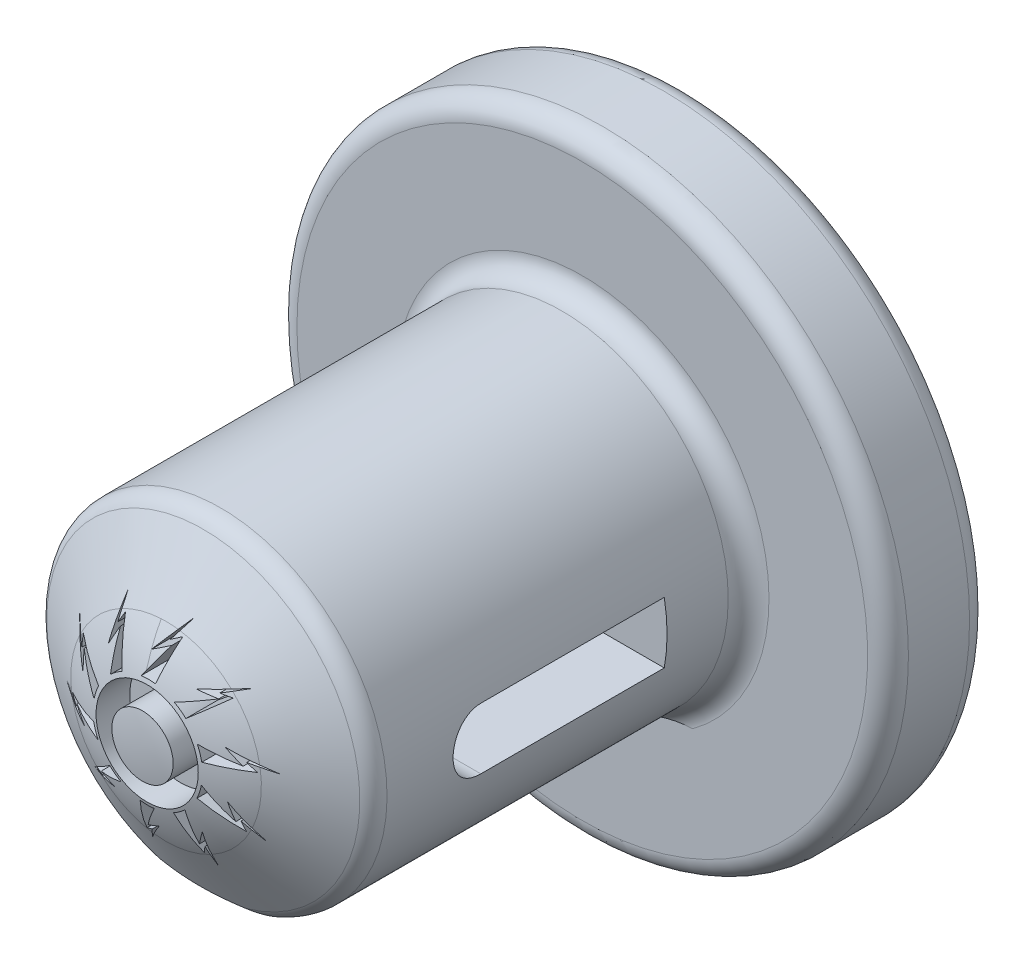
SolidWorks part; units mm, degrees
ref_plane "Alzado" through (0, 0, 0) normal (0, 0, 1) x (1, 0, 0)
ref_plane "Planta" through (0, 0, 0) normal (0, 1, 0) x (1, 0, 0)
ref_plane "Vista lateral" through (0, 0, 0) normal (1, 0, 0) x (0, 0, -1)
sketch "Croquis1" plane through (0, 0, 0) normal (0, 0, 1) x (1, 0, 0)
  line L0 (3.458, -7.3911) -> (-3.458, -7.3911)
  line L1 (2.71, -4.3911) -> (-2.71, -4.3911)
  arc A0 (2.71, -4.3911) -> (-2.71, -4.3911) centre (0, 0) ccw
  arc A1 (3.458, -7.3911) -> (-3.458, -7.3911) centre (0, 0) ccw
  point P7 (0, -4.3911)
  dimension "D1" = 10.32
  dimension "D2" = 5.42
  dimension "D3" = 3
extrude "Saliente-Extruir1" add sketch "Croquis1" along normal blind 23.3
sketch "Croquis2" plane through (0, 0, 0) normal (0, 0, -1) x (-1, 0, 0)
  line L0 (2.71, -4.3911) -> (-2.71, -4.3911) construction
  line L1 (2.71, -4.3911) -> (-2.71, -4.3911)
  circle A0 centre (0, 0) radius 15
  arc A1 (2.71, -4.3911) -> (-2.71, -4.3911) centre (0, 0) ccw construction
  arc A2 (2.71, -4.3911) -> (-2.71, -4.3911) centre (0, 0) ccw
  dimension "D1" = 30
extrude "Saliente-Extruir2" add sketch "Croquis2" against normal blind 5
sketch "Croquis3" plane through (0, 0, 0) normal (1, 0, 0) x (0, 0, -1)
  line L0 (-23.3, 0) -> (-23.3, 8.16)
  line L2 (-23.3, 8.16) -> (-25.4185, 4.6757)
  line L3 (-26.7284, 0) -> (-23.3, 0)
  arc A0 (-25.4185, 4.6757) -> (-26.7284, 0) centre (-17.7284, 0) ccw
  dimension "D2" = 9
  dimension "D1" = 31.3
revolve "Revolución1" add sketch "Croquis3" angle 360 about L3
sketch "Croquis4" plane through (0, 0, 23.3) normal (0, 0, -1) x (-1, 0, 0)
  line L1 (3.458, -7.3911) -> (-3.458, -7.3911)
  line L2 (3.458, -7.3911) -> (-3.458, -7.3911)
  arc A1 (-3.458, -7.3911) -> (3.458, -7.3911) centre (0, 0) ccw
  arc A2 (-3.458, -7.3911) -> (3.458, -7.3911) centre (0, 0) ccw
  dimension "D1" = 0
extrude "Cortar-Extruir1" cut sketch "Croquis4" against normal up to next
fillet "Redondeo3" radius 1 4 edges at (-15, 0, 0) (-15, 0, 5) (0, 8.16, 5) (0, 8.16, 23.3)
fillet "Redondeo2" radius 1 2 edges at (0, -4.3911, 0) (0, 5.16, 0)
ref_plane "Plano1" through (0, 0, 26.7284) normal (0, 0, 1) x (1, 0, 0)
sketch "Croquis5" plane through (0, 0, 26.7284) normal (0, 0, 1) x (1, 0, 0)
  line L0 (1.3026, 2.3441) -> (2.8816, 2.9738)
  line L1 (-0.324, 2.662) -> (0.5833, 4.0996)
  line L2 (0.5833, 4.0996) -> (-0.19, 3.662)
  line L3 (-0.19, 3.662) -> (1.0396, 5.192)
  line L4 (1.0396, 5.192) -> (0.4463, 4.2519)
  line L5 (0.4463, 4.2519) -> (0.876, 4.4951)
  line L6 (0.876, 4.4951) -> (0.376, 2.662)
  line L7 (2.8816, 2.9738) -> (1.9987, 3.0743)
  line L8 (1.9987, 3.0743) -> (3.8929, 3.5894)
  line L9 (3.8929, 3.5894) -> (2.8603, 3.1775)
  line L10 (2.8603, 3.1775) -> (3.3508, 3.1217)
  line L11 (3.3508, 3.1217) -> (1.8689, 1.9326)
  line L12 (2.4316, 1.1308) -> (4.0792, 0.7121)
  line L13 (4.0792, 0.7121) -> (3.4241, 1.3124)
  line L14 (3.4241, 1.3124) -> (5.2592, 0.6157)
  line L15 (5.2592, 0.6157) -> (4.1817, 0.8895)
  line L16 (4.1817, 0.8895) -> (4.5457, 0.5559)
  line L17 (4.5457, 0.5559) -> (2.6479, 0.465)
  line L18 (2.6319, -0.5144) -> (3.7187, -1.8216)
  line L19 (3.7187, -1.8216) -> (3.5415, -0.9509)
  line L20 (3.5415, -0.9509) -> (4.6166, -2.5932)
  line L21 (4.6166, -2.5932) -> (3.9059, -1.7384)
  line L22 (3.9059, -1.7384) -> (4.0044, -2.2222)
  line L23 (4.0044, -2.2222) -> (2.4155, -1.1802)
  line L24 (1.8268, -1.9632) -> (1.9378, -3.6595)
  line L25 (1.9378, -3.6595) -> (2.3062, -2.8509)
  line L26 (2.3062, -2.8509) -> (2.2107, -4.8115)
  line L27 (2.2107, -4.8115) -> (2.1381, -3.7022)
  line L28 (2.1381, -3.7022) -> (1.9334, -4.1515)
  line L29 (1.9334, -4.1515) -> (1.2605, -2.3746)
  line L30 (0.324, -2.662) -> (-0.5833, -4.0996)
  line L31 (-0.5833, -4.0996) -> (0.19, -3.662)
  line L32 (0.19, -3.662) -> (-1.0396, -5.192)
  line L33 (-1.0396, -5.192) -> (-0.4463, -4.2519)
  line L34 (-0.4463, -4.2519) -> (-0.876, -4.4951)
  line L35 (-0.876, -4.4951) -> (-0.376, -2.662)
  line L36 (-1.3026, -2.3441) -> (-2.8816, -2.9738)
  line L37 (-2.8816, -2.9738) -> (-1.9987, -3.0743)
  line L38 (-1.9987, -3.0743) -> (-3.8929, -3.5894)
  line L39 (-3.8929, -3.5894) -> (-2.8603, -3.1775)
  line L40 (-2.8603, -3.1775) -> (-3.3508, -3.1217)
  line L41 (-3.3508, -3.1217) -> (-1.8689, -1.9326)
  line L42 (-2.4316, -1.1308) -> (-4.0792, -0.7121)
  line L43 (-4.0792, -0.7121) -> (-3.4241, -1.3124)
  line L44 (-3.4241, -1.3124) -> (-5.2592, -0.6157)
  line L45 (-5.2592, -0.6157) -> (-4.1817, -0.8895)
  line L46 (-4.1817, -0.8895) -> (-4.5457, -0.5559)
  line L47 (-4.5457, -0.5559) -> (-2.6479, -0.465)
  line L48 (-2.6319, 0.5144) -> (-3.7187, 1.8216)
  line L49 (-3.7187, 1.8216) -> (-3.5415, 0.9509)
  line L50 (-3.5415, 0.9509) -> (-4.6166, 2.5932)
  line L51 (-4.6166, 2.5932) -> (-3.9059, 1.7384)
  line L52 (-3.9059, 1.7384) -> (-4.0044, 2.2222)
  line L53 (-4.0044, 2.2222) -> (-2.4155, 1.1802)
  line L54 (-1.8268, 1.9632) -> (-1.9378, 3.6595)
  line L55 (-1.9378, 3.6595) -> (-2.3062, 2.8509)
  line L56 (-2.3062, 2.8509) -> (-2.2107, 4.8115)
  line L57 (-2.2107, 4.8115) -> (-2.1381, 3.7022)
  line L58 (-2.1381, 3.7022) -> (-1.9334, 4.1515)
  line L59 (-1.9334, 4.1515) -> (-1.2605, 2.3746)
  circle A0 centre (0.026, -0.0152) radius 1.5
  circle A1 centre (0.026, -0.0152) radius 2.5
  arc A2 (0.376, 2.662) -> (-0.324, 2.662) centre (0.026, -0.0152) ccw
  arc A3 (1.8689, 1.9326) -> (1.3026, 2.3441) centre (0.0121, -0.0276) ccw
  arc A4 (2.6479, 0.465) -> (2.4316, 1.1308) centre (-0.0064, -0.0294) ccw
  arc A5 (2.4155, -1.1802) -> (2.6319, -0.5144) centre (-0.0225, -0.02) ccw
  arc A6 (1.2605, -2.3746) -> (1.8268, -1.9632) centre (-0.03, -0.003) ccw
  arc A7 (-0.376, -2.662) -> (0.324, -2.662) centre (-0.026, 0.0152) ccw
  arc A8 (-1.8689, -1.9326) -> (-1.3026, -2.3441) centre (-0.0121, 0.0276) ccw
  arc A9 (-2.6479, -0.465) -> (-2.4316, -1.1308) centre (0.0064, 0.0294) ccw
  arc A10 (-2.4155, 1.1802) -> (-2.6319, 0.5144) centre (0.0225, 0.02) ccw
  arc A11 (-1.2605, 2.3746) -> (-1.8268, 1.9632) centre (0.03, 0.003) ccw
  point P1 (0.026, 2.6848)
  point P4 (0.026, -0.0152)
  point P11 (0.026, -0.0152)
  point P38 (0.026, -0.0152)
  point P91 (0, 0)
  dimension "D1" = 3
  dimension "D12" = 2.7
  dimension "D9" = 5
  dimension "D2" = 0.2
  dimension "D3" = 1.9
  dimension "D4" = 1.7
  dimension "D5" = 0.7
  dimension "D6" = 0.5
  dimension "D7" = 1
  dimension "D8" = 2.53
  dimension "D10" = 0.566
  dimension "D11" = 0.6637
  dimension "D13" = 0.026
  dimension "D14" = 10
  dimension "D15" = 0.0064
extrude "Cortar-Extruir2" cut sketch "Croquis5" against normal blind 2
chamfer "Chaflán1" distance 0.5 angle 45 1 edges at (0, 5.16, 23.3)
ref_plane "Plano2" through (8.16, 0, 0) normal (1, 0, 0) x (0, 0, -1)
sketch "Croquis6" plane through (8.16, 0, 0) normal (1, 0, 0) x (0, 0, -1)
  line L0 (-18, 0) -> (-5, 0) construction
  line L1 (-18, 1.5) -> (-5, 1.5) construction
  line L2 (-18, -1.5) -> (-5, -1.5) construction
  line L3 (-23.3, -4.3911) -> (-23.3, 4.66) construction
  line L4 (-9, -1.5) -> (-9, 1.5)
  line L5 (-9, 1.5) -> (-18, 1.5)
  line L6 (-18, -1.5) -> (-9, -1.5)
  line L8 (-5, -7.3911) -> (-5, -8.16) construction
  arc A0 (-18, 1.5) -> (-18, -1.5) centre (-18, 0) ccw construction
  arc A1 (-5, -1.5) -> (-5, 1.5) centre (-5, 0) ccw construction
  arc A2 (-18, 1.5) -> (-18, -1.5) centre (-18, 0) ccw
  point P3 (-11.5, 0)
  point P8 (-19.5, 0)
  point P11 (-3.5, 0)
  dimension "D1" = 3
  dimension "D2" = 3.8
  dimension "D3" = 16
  dimension "D4" = 4
extrude "Cortar-Extruir3" cut sketch "Croquis6" against normal up to next
